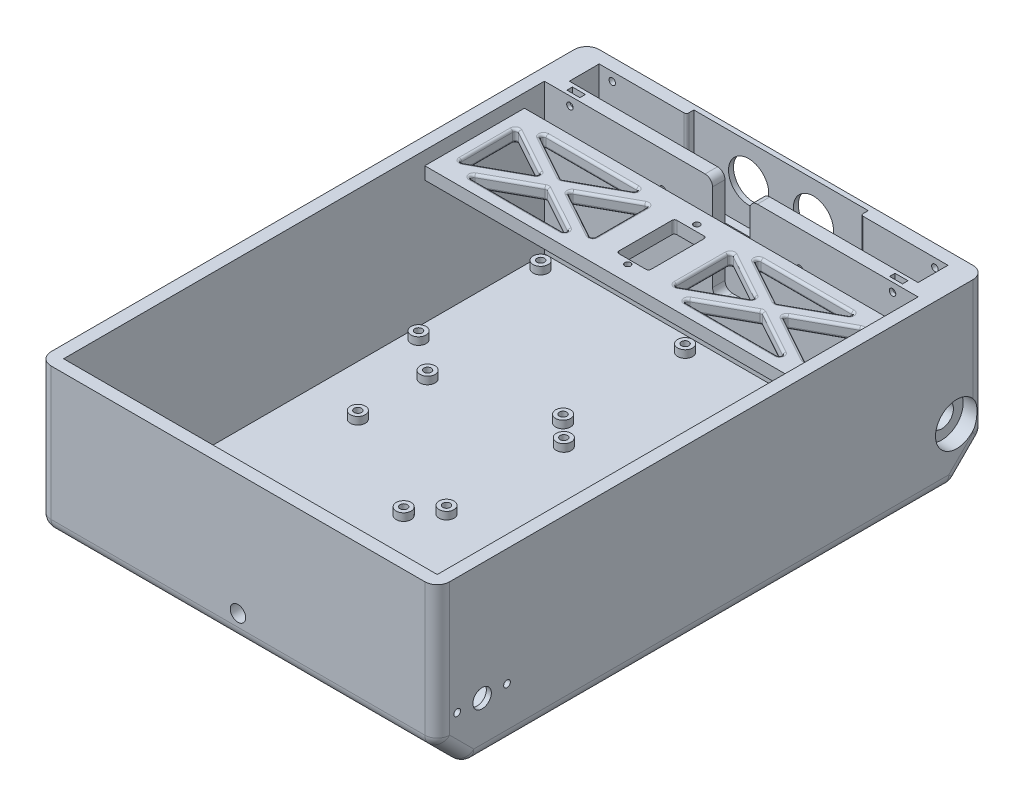
SolidWorks part; units mm, degrees
ref_plane "Front Plane" through (0, 0, 0) normal (0, 0, 1) x (1, 0, 0)
ref_plane "Top Plane" through (0, 0, 0) normal (0, 1, 0) x (1, 0, 0)
ref_plane "Right Plane" through (0, 0, 0) normal (1, 0, 0) x (0, 0, -1)
sketch "Main Body" plane through (0, 0, 0) normal (0, 1, 0) x (1, 0, 0)
  line L0 (-75, 110) -> (75, 110)
  line L1 (-75, -105) -> (75, -105)
  line L2 (-75, -105) -> (-75, 105)
  line L3 (-75, 105) -> (75, 105)
  line L4 (75, -105) -> (75, 105)
  line L5 (-75, -105) -> (75, 105) construction
  line L6 (-75, 105) -> (75, -105) construction
  line L7 (80, -105) -> (80, 105)
  line L8 (-75, -110) -> (75, -110)
  line L9 (-80, -105) -> (-80, 105)
  line L10 (-80, -110) -> (80, -110) construction
  line L11 (-80, -110) -> (-80, 110) construction
  line L12 (80, -110) -> (80, 110) construction
  line L13 (-80, 110) -> (80, 110) construction
  arc A0 (-75, -110) -> (-80, -105) centre (-75, -105) cw
  arc A1 (80, -105) -> (75, -110) centre (75, -105) cw
  arc A2 (75, 110) -> (80, 105) centre (75, 105) cw
  arc A3 (-75, 110) -> (-80, 105) centre (-75, 105) ccw
  point P0 (0, 0)
  dimension "D4" = 5
  dimension "D1" = 75
  dimension "D2" = 210
  dimension "D3" = 5
extrude "Boss-Extrude1" add sketch "Main Body" along normal blind 8 contours L1 L4 L3 L2 | L9 L8 L7 L0 L4 L1 L2 L3 region at (0, 0, -107.2797) region at (0, 0, 0)
extrude "Boss-Extrude3" add sketch "Main Body<4>" along normal blind 60 from surface starting at face at (0, 8, 0)
sketch "Main Body<4>" plane through (0, 0, 0) normal (0, 1, 0) x (1, 0, 0) same geometry as "Main Body"
sketch "Sketch1" plane through (75, 0, 0) normal (-1, 0, 0) x (0, 0, 1)
  line L0 (105, 68) -> (105, 8) construction
  line L1 (-105, 8) -> (105, 8) construction
  line L2 (79, 15.5) -> (105, 15.5)
  line L3 (79, 8) -> (105, 8)
  line L4 (79, 8) -> (79, 34)
  line L5 (79, 34) -> (105, 34)
  line L6 (105, 8) -> (105, 34)
  line L7 (79, 8) -> (105, 34) construction
  line L8 (79, 34) -> (105, 8) construction
  circle A0 centre (92, 21) radius 13
  line M2 (-105, 8) -> (105, 8)
  line M3 (105, 8) -> (105, 68)
  dimension "D1" = 26
  dimension "D2" = 7.5
extrude "Boss-Extrude4" add sketch "Sketch1" along normal up to surface (150 mm away) contours A0 L4 M2 | A0 L3 M3 region at (75, 10.5201, 82.0674) region at (75, 10.5201, 101.9326) up to face at (-75, 38, 0)
sketch "Sketch2" plane through (0, 0, 0) normal (1, 0, 0) x (0, 0, -1)
  line L0 (-105, 68) -> (-105, 15.5) construction
  line L1 (-105, 8) -> (-79, 8)
  line L2 (-105, 8) -> (-105, 15.5)
  line L3 (-105, 15.5) -> (-79, 15.5)
  line L4 (-79, 8) -> (-79, 15.5)
  line L5 (105, 8) -> (-79, 8) construction
  line L6 (-79, 8) -> (-79, 15.5) construction
  line L7 (-79, 15.5) -> (-80.2208, 15.5) construction
extrude "Cut-Extrude1" cut sketch "Sketch2" against normal mid plane 12
sketch "Sketch3" plane through (0, 8, 0) normal (0, 1, 0) x (1, 0, 0)
  line L0 (75, -105) -> (-75, -105) construction
  line L1 (-4, -79) -> (-11, -79)
  line L2 (-4, -79) -> (-4, -105)
  line L3 (-4, -105) -> (-11, -105)
  line L4 (-11, -79) -> (-11, -105)
  line L5 (0, 0) -> (0, -105) construction
  line L6 (-75, -79) -> (-6, -79) construction
  line L7 (11, -79) -> (11, -105)
  line L8 (4, -105) -> (11, -105)
  line L9 (4, -79) -> (4, -105)
  line L10 (4, -79) -> (11, -79)
  line L11 (-6, -103.7792) -> (-6, -92) construction
  dimension "D1" = 5
  dimension "D2" = 4
extrude "Boss-Extrude5" add sketch "Sketch3" along normal blind 20
sketch "Sketch4" plane through (0, 8, 0) normal (0, 1, 0) x (1, 0, 0)
  line L0 (-75, -105) -> (-75, 105) construction
  line L1 (-75, 93) -> (75, 93)
  line L2 (-75, 93) -> (-75, 88)
  line L3 (-75, 88) -> (75, 88)
  line L4 (75, 93) -> (75, 88)
  line L5 (75, 105) -> (75, -105) construction
  line L6 (-75, 105) -> (75, 105) construction
  dimension "D1" = 17
  dimension "D2" = 5
extrude "Boss-Extrude6" add sketch "Sketch4" along normal up to surface (60 mm away) up to face at (0, 68, 0)
sketch "Sketch5" plane through (80, 0, 0) normal (1, 0, 0) x (0, 0, -1)
  circle A0 centre (-92, 21) radius 3.5 construction
  circle A1 centre (-92, 21) radius 3.5
  circle A2 centre (-92, 21) radius 3.7
  dimension "D1" = 0.2
extrude "Cut-Extrude4" cut sketch "Sketch5" against normal up to next contours A1 | A2 A1 region at (80, 21, 92) region at (80, 21, 95.5953)
sketch "Sketch6" plane through (-75, 0, 0) normal (1, 0, 0) x (0, 0, -1)
  circle A0 centre (-92, 21) radius 13
  dimension "D1" = 26
extrude "Cut-Extrude5" cut sketch "Sketch6" against normal offset from surface (3 mm away) 2 up to face at (-80, 34, 0)
mirror "Mirror1" about plane through (0, 0, 0) normal (1, 0, 0) of "Cut-Extrude4"
sketch "Sketch8" plane through (75, 0, 0) normal (-1, 0, 0) x (0, 0, 1)
  circle A0 centre (92, 21) radius 13
  dimension "D1" = 26
extrude "Cut-Extrude6" cut sketch "Sketch8" against normal offset from surface (3 mm away) 2 up to face at (80, 21, 88.3)
sketch "Sketch10" plane through (80, 0, 0) normal (1, 0, 0) x (0, 0, -1)
  circle A1 centre (-82, 21) radius 1.25
  circle A2 centre (-82, 21) radius 1.25
  circle A3 centre (-102, 21) radius 1.25
  circle A4 centre (-102, 21) radius 1.25
  circle A5 centre (-92, 21) radius 12.5
  circle A6 centre (-92, 21) radius 12.5
  circle A63 centre (-102, 21) radius 1.35
  circle A64 centre (-82, 21) radius 1.35
  dimension "D1" = 0
  dimension "D2" = 0
  dimension "D3" = 0
  dimension "D4" = 0.1
  dimension "D5" = 0.1
extrude "Cut-Extrude7" cut sketch "Sketch10" against normal up to next contours A2 | A64 A2 | A4 | A63 A4 region at (80, 21, 82) region at (80, 21, 102) region at (80, 21, 103.3118) region at (80, 21, 83.3118)
mirror "Mirror3" about plane through (0, 0, 0) normal (1, 0, 0) of "Cut-Extrude7"
sketch "Sketch11" plane through (80, 0, 0) normal (1, 0, 0) x (0, 0, -1)
  circle A0 centre (98.55, 21.05) radius 4.45 construction
  circle A1 centre (98.55, 21.05) radius 4.45
  circle A3 centre (98.55, 21.05) radius 4.65
  dimension "D1" = 0.2
extrude "Cut-Extrude10" cut sketch "Sketch11" against normal through all contours A1 | A3 A1 region at (80, 21.05, -98.55) region at (80, 21.05, -94.0315)
sketch "Sketch12" plane through (-75, 0, 0) normal (1, 0, 0) x (0, 0, -1)
  line L0 (93, 8) -> (105, 8) construction
  line L1 (93, 68) -> (105, 68)
  line L2 (93, 68) -> (93, 8)
  line L3 (93, 8) -> (105, 8)
  line L4 (105, 68) -> (105, 8)
  line L6 (93, 68) -> (93, 8) construction
  line L7 (93, 68) -> (105, 68) construction
  circle A2 centre (98.55, 21.05) radius 4.65 construction
  circle A3 centre (98.55, 21.05) radius 4.65
extrude "Boss-Extrude7" add sketch "Sketch12" along normal blind 5
sketch "Sketch13" plane through (-80, 0, 0) normal (-1, 0, 0) x (0, 0, 1)
  circle A0 centre (-98.55, 21.05) radius 8.55
  circle A2 centre (-98.55, 21.05) radius 4.65 construction
  dimension "D1" = 17.1
extrude "Cut-Extrude11" cut sketch "Sketch13" against normal blind 6
mirror "Mirror4" about plane through (0, 0, 0) normal (1, 0, 0) of "Boss-Extrude7", "Cut-Extrude11"
sketch "Sketch14" plane through (0, 8, 0) normal (0, 1, 0) x (1, 0, 0)
  line L0 (-4, -105) -> (-4, -79) construction
  line L1 (-4, -95) -> (4, -95)
  line L2 (-4, -95) -> (-4, -105)
  line L3 (-4, -105) -> (4, -105)
  line L4 (4, -95) -> (4, -105)
  dimension "D1" = 10
extrude "Boss-Extrude9" add sketch "Sketch14" along normal blind 5
sketch "Sketch15" plane through (0, 0, 110) normal (0, 0, 1) x (1, 0, 0)
  arc A0 (-3, 19.5) -> (3, 19.5) centre (0, 19.5) ccw construction
  arc A1 (-3, 19.5) -> (3, 19.5) centre (0, 19.5) ccw
  arc A2 (3, 19.5) -> (-3, 19.5) centre (0, 19.5) ccw construction
  arc A3 (3, 19.5) -> (-3, 19.5) centre (0, 19.5) ccw
  arc A4 (3.1, 19.5) -> (-3.1, 19.5) centre (0, 19.5) ccw
  arc A5 (-3.1, 19.5) -> (3.1, 19.5) centre (0, 19.5) ccw
  dimension "D1" = 0.1
extrude "Cut-Extrude12" cut sketch "Sketch15" against normal up to next contours A1 A3 | A4 A5 A3 A1 region at (0, 19.5, 110) region at (0, 16.4877, 110)
sketch "Sketch16" plane through (0, 0, 0) normal (0, -1, 0) x (1, 0, 0)
  circle A0 centre (-12.5, -82) radius 1.475 construction
  circle A1 centre (-70.5, -82) radius 1.475 construction
  circle A2 centre (-70.5, -33) radius 1.475 construction
  circle A3 centre (-12.5, -33) radius 1.475 construction
  circle A4 centre (-4.2, -25) radius 1.475 construction
  circle A5 centre (-55, -21.12) radius 1.475 construction
  circle A6 centre (-55, 6.88) radius 1.475 construction
  circle A7 centre (-4.2, 22.08) radius 1.475 construction
  circle A8 centre (-12.3, 31.18) radius 1.475 construction
  circle A9 centre (24.2, 31.18) radius 1.475 construction
  circle A10 centre (37.8459, 24.117) radius 1.475 construction
  circle A11 centre (59.5541, 24.117) radius 1.475 construction
  circle A12 centre (59.5541, 68.243) radius 1.475 construction
  circle A13 centre (37.8459, 68.243) radius 1.475 construction
  circle A14 centre (24.2, 67.68) radius 1.475 construction
  circle A15 centre (-12.3, 67.68) radius 1.475 construction
  circle A16 centre (-12.5, -82) radius 1.475
  circle A17 centre (-70.5, -82) radius 1.475
  circle A18 centre (-70.5, -33) radius 1.475
  circle A19 centre (-12.5, -33) radius 1.475
  circle A20 centre (-4.2, -25) radius 1.475
  circle A21 centre (-55, -21.12) radius 1.475
  circle A22 centre (-55, 6.88) radius 1.475
  circle A23 centre (-4.2, 22.08) radius 1.475
  circle A24 centre (-12.3, 31.18) radius 1.475
  circle A25 centre (24.2, 31.18) radius 1.475
  circle A26 centre (37.8459, 24.117) radius 1.475
  circle A27 centre (59.5541, 24.117) radius 1.475
  circle A28 centre (59.5541, 68.243) radius 1.475
  circle A29 centre (37.8459, 68.243) radius 1.475
  circle A30 centre (24.2, 67.68) radius 1.475
  circle A31 centre (-12.3, 67.68) radius 1.475
extrude "Cut-Extrude13" cut sketch "Sketch16" against normal up to next
sketch "Sketch17" plane through (0, 8, 0) normal (0, 1, 0) x (1, 0, 0)
  line L0 (0, 88) -> (0, -110) construction
  line L1 (-75, 88) -> (75, 88) construction
  line L2 (75, -110) -> (-75, -110) construction
  line L3 (-75, 4.5) -> (75, 4.5) construction
  line L7 (-75, -79) -> (-75, 88) construction
  line L8 (75, 88) -> (75, -79) construction
  circle A0 centre (-70.5, 82) radius 3
  circle A1 centre (-12.5, 82) radius 3
  circle A2 centre (-12.3, -67.68) radius 1.475
  circle A3 centre (-12.3, -67.68) radius 1.475
  circle A4 centre (24.2, -67.68) radius 1.475
  circle A5 centre (24.2, -67.68) radius 1.475
  circle A6 centre (37.8459, -68.243) radius 1.475
  circle A7 centre (37.8459, -68.243) radius 1.475
  circle A8 centre (59.5541, -68.243) radius 1.475
  circle A9 centre (59.5541, -68.243) radius 1.475
  circle A10 centre (59.5541, -24.117) radius 1.475
  circle A11 centre (59.5541, -24.117) radius 1.475
  circle A12 centre (37.8459, -24.117) radius 1.475
  circle A13 centre (37.8459, -24.117) radius 1.475
  circle A14 centre (24.2, -31.18) radius 1.475
  circle A15 centre (24.2, -31.18) radius 1.475
  circle A16 centre (-12.3, -31.18) radius 1.475
  circle A17 centre (-12.3, -31.18) radius 1.475
  circle A18 centre (-4.2, -22.08) radius 1.475
  circle A19 centre (-4.2, -22.08) radius 1.475
  circle A20 centre (-55, -6.88) radius 1.475
  circle A21 centre (-55, -6.88) radius 1.475
  circle A22 centre (-55, 21.12) radius 1.475
  circle A23 centre (-55, 21.12) radius 1.475
  circle A24 centre (-4.2, 25) radius 1.475
  circle A25 centre (-4.2, 25) radius 1.475
  circle A26 centre (-12.5, 33) radius 1.475
  circle A27 centre (-12.5, 33) radius 1.475
  circle A28 centre (-70.5, 33) radius 1.475
  circle A29 centre (-70.5, 33) radius 1.475
  circle A30 centre (-70.5, 82) radius 1.475
  circle A31 centre (-70.5, 82) radius 1.475
  circle A32 centre (-12.5, 82) radius 1.475
  circle A33 centre (-12.5, 82) radius 1.475
  circle A34 centre (-70.5, 33) radius 3
  circle A35 centre (-55, 21.12) radius 3
  circle A36 centre (-12.5, 33) radius 3
  circle A37 centre (-4.2, 25) radius 3
  circle A38 centre (-55, -6.88) radius 3
  circle A39 centre (-4.2, -22.08) radius 3
  circle A40 centre (-12.3, -31.18) radius 3
  circle A41 centre (24.2, -31.18) radius 3
  circle A42 centre (37.8459, -24.117) radius 3
  circle A43 centre (59.5541, -24.117) radius 3
  circle A44 centre (-12.3, -67.68) radius 3
  circle A45 centre (24.2, -67.68) radius 3
  circle A46 centre (37.8459, -68.243) radius 3
  circle A47 centre (59.5541, -68.243) radius 3
  dimension "D1" = 6
  dimension "D2" = 0
  dimension "D3" = 0
  dimension "D4" = 0
  dimension "D5" = 0
  dimension "D6" = 0
  dimension "D7" = 0
  dimension "D8" = 0
  dimension "D9" = 0
  dimension "D10" = 0
  dimension "D11" = 0
  dimension "D12" = 0
  dimension "D13" = 0
  dimension "D14" = 0
  dimension "D15" = 0
  dimension "D16" = 0
  dimension "D17" = 0
extrude "Boss-Extrude10" add sketch "Sketch17" along normal blind 3
sketch "Sketch18" plane through (75, 0, 0) normal (-1, 0, 0) x (0, 0, 1)
  line L1 (-80, 62.6) -> (-40, 62.6)
  line L2 (-80, 62.6) -> (-80, 57.6)
  line L3 (-80, 57.6) -> (-40, 57.6)
  line L4 (-40, 62.6) -> (-40, 57.6)
  line L5 (-88, 68) -> (105, 68) construction
  dimension "D1" = 5
  dimension "D2" = 30
  dimension "D3" = 40
  dimension "D4" = 5.4
extrude "Boss-Extrude11" add sketch "Sketch18" along normal up to next
sketch "Sketch19" plane through (0, 68, 0) normal (0, 1, 0) x (1, 0, 0)
  line L1 (-6.425, 71.625) -> (6.425, 71.625)
  line L2 (-6.425, 71.625) -> (-6.425, 48.375)
  line L3 (-6.425, 48.375) -> (6.425, 48.375)
  line L4 (6.425, 71.625) -> (6.425, 48.375)
  line L12 (-75, 80) -> (-75, 40)
  line L13 (-75, 40) -> (75, 40)
  line L14 (75, 40) -> (75, 80)
  line L15 (75, 80) -> (-75, 80)
  line L16 (-75, 80) -> (-75, 40)
  line L17 (-75, 40) -> (75, 40)
  line L18 (75, 40) -> (75, 80)
  line L19 (75, 80) -> (-75, 80)
  point P4 (0, 71.625)
  point P8 (0, 80)
  point P12 (6.425, 60)
  point P13 (75, 60)
  dimension "D1" = 23.25
  dimension "D2" = 12.85
  dimension "D3" = 0
extrude "Cut-Extrude14" cut sketch "Sketch19" against normal up to next contours L4 L1 L2 L3 region at (0, 68, -60)
sketch "Sketch21" plane through (0, 0, -110) normal (0, 0, -1) x (-1, 0, 0)
  circle A1 centre (-64.75, 64.5) radius 1.3
  circle A2 centre (-64.75, 64.5) radius 1.3
  circle A3 centre (64.75, 64.5) radius 1.3
  circle A4 centre (64.75, 64.5) radius 1.3
  dimension "D1" = 0
  dimension "D2" = 0
extrude "Cut-Extrude16" cut sketch "Sketch21" against normal up to surface (22 mm away) up to face at (0, 38, -88)
ref_plane "Plane1" through (0, 0, -90.5) normal (0, 0, -1) x (-1, 0, 0)
sketch "Sketch22" plane through (0, 0, -90.5) normal (0, 0, -1) x (-1, 0, 0)
  line L0 (-67.35, 66.0011) -> (-67.35, 68)
  line L1 (-62.15, 66.0011) -> (-64.75, 67.5022)
  line L2 (-64.75, 67.5022) -> (-67.35, 66.0011)
  line L3 (-67.35, 66.0011) -> (-67.35, 62.9989)
  line L4 (-67.35, 62.9989) -> (-64.75, 61.4978)
  line L5 (-64.75, 61.4978) -> (-62.15, 62.9989)
  line L6 (-62.15, 62.9989) -> (-62.15, 66.0011)
  line L7 (-67.35, 68) -> (-62.15, 68)
  line L8 (-62.15, 68) -> (-62.15, 66.0011)
  line L9 (70, 68) -> (-70, 68) construction
  line L10 (0, 0) -> (0, 68) construction
  line L11 (75, 68) -> (-75, 68) construction
  line L12 (64.75, 61.4978) -> (62.15, 62.9989)
  line L13 (67.35, 62.9989) -> (64.75, 61.4978)
  line L14 (64.75, 67.5022) -> (67.35, 66.0011)
  line L15 (67.35, 66.0011) -> (67.35, 62.9989)
  line L16 (67.35, 66.0011) -> (67.35, 68)
  line L17 (62.15, 62.9989) -> (62.15, 66.0011)
  line L18 (62.15, 68) -> (62.15, 66.0011)
  line L19 (67.35, 68) -> (62.15, 68)
  line L20 (62.15, 66.0011) -> (64.75, 67.5022)
  circle A0 centre (-64.75, 64.5) radius 2.6 construction
  dimension "D1" = 5.2
extrude "Cut-Extrude17" cut sketch "Sketch22" against normal mid plane 2.2 contours L20 L17 L12 L13 L15 L14 | L18 L20 L14 L16 L19 | L5 L6 L1 L2 L3 L4 | L8 L7 L0 L2 L1 region at (67.2943, 67.0006, -90.5) region at (64.75, 64.5, -90.5) region at (-64.75, 64.5, -90.5) region at (-62.2057, 67.0006, -90.5)
sketch "Sketch23" plane through (0, 0, -110) normal (0, 0, -1) x (-1, 0, 0)
  circle A0 centre (64.75, 64.5) radius 2.5
  circle A1 centre (-64.75, 64.5) radius 2.5
  dimension "D1" = 5
  dimension "D2" = 5
extrude "Cut-Extrude18" cut sketch "Sketch23" against normal mid plane 2.5
sketch "Sketch24" plane through (0, 62.6, 0) normal (0, 1, 0) x (1, 0, 0)
  circle A0 centre (0, 46.475) radius 1.2002
  arc A1 (0.4, 45.5583) -> (-0.4, 45.5583) centre (0, 46.475) ccw construction
  circle A2 centre (0, 74.175) radius 1.2002
  arc A3 (-0.4, 75.0917) -> (0, 73.1748) centre (0, 74.175) ccw construction
  point P5 (0.4, 45.5583)
  dimension "D1" = 0.2
extrude "Cut-Extrude19" cut sketch "Sketch24" against normal up to next
sketch "Sketch25" plane through (0, 62.6, 0) normal (0, 1, 0) x (1, 0, 0)
  line L1 (-11.3, 80) -> (11.3, 80)
  line L2 (-11.3, 80) -> (-11.3, 40)
  line L3 (-11.3, 40) -> (11.3, 40)
  line L4 (-75, 80) -> (-75, 40)
  line L5 (-75, 40) -> (75, 40)
  line L6 (75, 40) -> (75, 80)
  line L7 (75, 80) -> (-75, 80)
  line L8 (-75, 80) -> (-75, 40)
  line L9 (-75, 40) -> (75, 40)
  line L10 (75, 40) -> (75, 80)
  line L11 (75, 80) -> (-75, 80)
  line L12 (11.3, 80) -> (11.3, 40)
  line L13 (-11.3, 80) -> (11.3, 40) construction
  line L14 (-11.3, 40) -> (11.3, 80) construction
  line L15 (0, 80) -> (0, 40) construction
  line L16 (70, 75) -> (70, 45)
  line L17 (-70, 75) -> (-16.3, 75)
  line L18 (-70, 75) -> (-70, 45)
  line L19 (-70, 45) -> (-16.3, 45)
  line L20 (-16.3, 75) -> (-16.3, 45)
  line L21 (-70, 75) -> (-16.3, 45) construction
  line L22 (-70, 45) -> (-16.3, 75) construction
  line L23 (70, 75) -> (16.3, 45) construction
  line L24 (70, 45) -> (16.3, 75) construction
  line L25 (70, 75) -> (16.3, 75)
  line L26 (16.3, 75) -> (16.3, 45)
  line L27 (70, 45) -> (16.3, 45)
  line L28 (-75, 60) -> (-11.3, 60) construction
  line L29 (75, 60) -> (11.3, 60) construction
  line L30 (-70, 71.9362) -> (-48.3314, 60)
  line L31 (-16.3, 71.9362) -> (-37.9686, 60)
  line L32 (70, 71.9362) -> (48.3314, 60)
  line L33 (-48.3314, 60) -> (-70, 48.0638)
  line L34 (48.3314, 60) -> (70, 48.0638)
  line L35 (-65.199, 45) -> (-43.15, 57.1458)
  line L36 (65.199, 45) -> (43.15, 57.1458)
  line L37 (-43.15, 57.1458) -> (-21.101, 45)
  line L38 (43.15, 57.1458) -> (21.101, 45)
  line L39 (16.3, 71.9362) -> (37.9686, 60)
  line L40 (-37.9686, 60) -> (-16.3, 48.0638)
  line L41 (37.9686, 60) -> (16.3, 48.0638)
  line L42 (-65.199, 75) -> (-43.15, 62.8542)
  line L43 (65.199, 75) -> (43.15, 62.8542)
  line L44 (-43.15, 62.8542) -> (-21.101, 75)
  line L45 (43.15, 62.8542) -> (21.101, 75)
  line L46 (-75, 40) -> (-75, 80) construction
  line L47 (-75, 40) -> (75, 40) construction
  point P2 (0, 60)
  point P9 (-43.15, 60)
  point P10 (75, 60)
  point P24 (43.15, 60)
  point P62 (-54.1745, 68.9271)
  dimension "D2" = 150
  dimension "D3" = 5
  dimension "D4" = 5
  dimension "D5" = 5
  dimension "D6" = 26.6686
  dimension "D7" = 96.101
  dimension "D1" = 0
extrude "Cut-Extrude21" cut sketch "Sketch25" against normal up to next contours L37 L35 L19 | L33 L30 L18 | L42 L44 L17 | L31 L40 L20 | L41 L39 L26 | L45 L43 L25 | L36 L38 L27 | L32 L34 L16 region at (62.7771, 62.6, -60) region at (43.15, 62.6, -70.9514) region at (43.15, 62.6, -49.0486) region at (23.5229, 62.6, -60) region at (-43.15, 62.6, -70.9514) region at (-62.7771, 62.6, -60) region at (-23.5229, 62.6, -60) region at (-43.15, 62.6, -49.0486)
sketch "Sketch26" plane through (-80, 0, 0) normal (-1, 0, 0) x (0, 0, 1)
  line L0 (-110, 12.58) -> (-97.42, 0)
  line L1 (-110, 68) -> (-110, 0) construction
  line L2 (105, 0) -> (-105, 0) construction
  line L3 (-97.42, 0) -> (-92.42, 0)
  line L4 (-92.42, 0) -> (-110, 17.58)
  line L5 (-110, 17.58) -> (-110, 12.58)
  line L6 (-110, 12.58) -> (-110, 0)
  line L7 (-110, 0) -> (-97.42, 0)
  circle A1 centre (-98.55, 21.05) radius 8.55 construction
  line M5 (-105, 15.4375) -> (-105, 0)
  line M6 (-105, 0) -> (105, 0)
  dimension "D1" = 2
  dimension "D2" = 5
  dimension "D3" = 45
extrude "Cut-Extrude22" cut sketch "Sketch26" against normal up to next contours L6 L7 L0 M5 | L0 M5 M6 region at (-80, 5.1434, -107.7067) region at (-80, 2.5267, -102.4733)
mirror "Mirror5" about plane through (0, 0, 0) normal (0, 0, 1) of "Cut-Extrude22"
fillet "Fillet1" radius 5 14 edges at (80, 3.79, -101.21) (78.5355, 11.1156, -108.5355) (-80, 3.79, -101.21) (-78.5355, 11.1156, -108.5355) (80, 3.79, 101.21) (78.5355, 11.1156, 108.5355) (-80, 3.79, 101.21) (-78.5355, 11.1156, 108.5355) (0, 0, -97.42) (0, 12.58, -110) (0, 0, 97.42) (0, 12.58, 110) (-80, 0, 0) (80, 0, 0)
fillet "Fillet2" radius 1 76 edges at (-32.1255, 57.6, -51.0729) (-32.1255, 62.6, -51.0729) (-21.101, 60.1, -45) (-43.15, 62.6, -45) (-43.15, 57.6, -45) (-54.1745, 57.6, -51.0729) (-65.199, 60.1, -45) (-54.1745, 62.6, -51.0729) (-43.15, 60.1, -57.1458) (32.1255, 57.6, -68.9271) (32.1255, 62.6, -68.9271) (21.101, 60.1, -75) (43.15, 62.6, -75) (43.15, 57.6, -75) (54.1745, 57.6, -68.9271) (65.199, 60.1, -75) (54.1745, 62.6, -68.9271) (43.15, 60.1, -62.8542) (54.1745, 62.6, -51.0729) (54.1745, 57.6, -51.0729) (43.15, 57.6, -45) (65.199, 60.1, -45) (43.15, 62.6, -45) (21.101, 60.1, -45) (32.1255, 62.6, -51.0729) (43.15, 60.1, -57.1458) (32.1255, 57.6, -51.0729) (59.1657, 62.6, -65.9681) (59.1657, 57.6, -65.9681) (70, 57.6, -60) (70, 60.1, -71.9362) (70, 62.6, -60) (70, 60.1, -48.0638) (59.1657, 62.6, -54.0319) (48.3314, 60.1, -60) (59.1657, 57.6, -54.0319) (-54.1745, 62.6, -68.9271) (-54.1745, 57.6, -68.9271) (-43.15, 57.6, -75) (-65.199, 60.1, -75) (-43.15, 62.6, -75) (-21.101, 60.1, -75) (-32.1255, 62.6, -68.9271) (-43.15, 60.1, -62.8542) (-32.1255, 57.6, -68.9271) (-59.1657, 57.6, -54.0319) (-59.1657, 62.6, -54.0319) (-70, 60.1, -48.0638) (-70, 62.6, -60) (-70, 57.6, -60) (-59.1657, 57.6, -65.9681) (-70, 60.1, -71.9362) (-59.1657, 62.6, -65.9681) (-48.3314, 60.1, -60) (-27.1343, 62.6, -65.9681) (-27.1343, 57.6, -65.9681) (-16.3, 57.6, -60) (-16.3, 60.1, -71.9362) (-16.3, 62.6, -60) (-16.3, 60.1, -48.0638) (-27.1343, 62.6, -54.0319) (-37.9686, 60.1, -60) (-27.1343, 57.6, -54.0319) (27.1343, 57.6, -54.0319) (27.1343, 62.6, -54.0319) (16.3, 60.1, -48.0638) (16.3, 62.6, -60) (16.3, 57.6, -60) (27.1343, 57.6, -65.9681) (16.3, 60.1, -71.9362) (27.1343, 62.6, -65.9681) (37.9686, 60.1, -60) (6.425, 60.1, -48.375) (-6.425, 60.1, -48.375) (-6.425, 60.1, -71.625) (6.425, 60.1, -71.625)
sketch "Sketch33" plane through (0, 0, -110) normal (0, 0, -1) x (-1, 0, 0)
  circle A0 centre (-13, 53.9999) radius 8.075
  circle A1 centre (13, 53.9999) radius 8.075
  circle A2 centre (-13, 53.9999) radius 7.3 construction
  circle A3 centre (13, 53.9999) radius 7.3 construction
  dimension "D1" = 16.15
extrude "Cut-Extrude27" cut sketch "Sketch33" against normal up to next
sketch "Sketch34" plane through (0, 0, -93) normal (0, 0, -1) x (-1, 0, 0)
  circle A0 centre (27.525, 54) radius 1.3 construction
  circle A1 centre (27.525, 54) radius 1.3
  circle A2 centre (-27.525, 54) radius 1.3 construction
  circle A3 centre (-27.525, 54) radius 1.3
extrude "Cut-Extrude28" cut sketch "Sketch34" against normal up to next
sketch "Sketch35" plane through (0, 68, 0) normal (0, 1, 0) x (1, 0, 0)
  line L0 (70, 93) -> (-70, 93) construction
  line L1 (-7.5, 93) -> (7.5, 93)
  line L2 (-7.5, 93) -> (-7.5, 88)
  line L3 (-7.5, 88) -> (7.5, 88)
  line L4 (7.5, 93) -> (7.5, 88)
  line L5 (-7.5, 93) -> (7.5, 88) construction
  line L6 (-7.5, 88) -> (7.5, 93) construction
  line L7 (-75, 88) -> (75, 88) construction
  point P0 (0, 90.5)
  dimension "D1" = 15
extrude "Cut-Extrude29" cut sketch "Sketch35" against normal offset from surface (41 mm away) 19 up to face at (37.8459, 8, 71.243)
fillet "Fillet4" radius 3 9 edges at (0, 8, 95) (-7.5, 28, 79) (-7.5, 28, 105) (7.5, 28, 105) (7.5, 28, 79) (-7.5, 68, -90.5) (7.5, 68, -90.5) (-7.5, 27, -90.5) (7.5, 27, -90.5)
fillet "Fillet5" radius 1 1 edges at (0, 13, 95)
sketch "Sketch36" plane through (0, 68, 0) normal (0, 1, 0) x (1, 0, 0)
  line L0 (-70, 105) -> (70, 105) construction
  line L1 (-35, 108) -> (35, 108)
  line L2 (-35, 108) -> (-35, 105)
  line L3 (-35, 105) -> (35, 105)
  line L4 (35, 108) -> (35, 105)
  line L5 (-75, 110) -> (75, 110) construction
  point P6 (0, 108)
  dimension "D1" = 70
  dimension "D2" = 2
extrude "Cut-Extrude30" cut sketch "Sketch36" against normal blind 30
fillet "Fillet6" radius 1 2 edges at (35, 53, -105) (-35, 53, -105)
